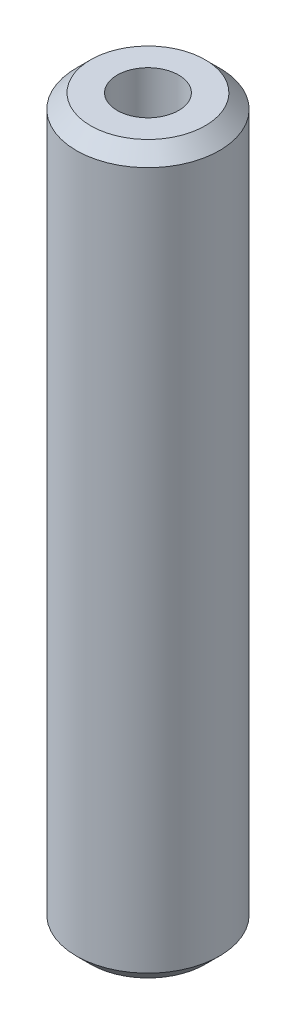
SolidWorks part; units mm, degrees
ref_plane "Front Plane" through (0, 0, 0) normal (0, 0, 1) x (1, 0, 0)
ref_plane "Top Plane" through (0, 0, 0) normal (0, 1, 0) x (1, 0, 0)
ref_plane "Right Plane" through (0, 0, 0) normal (1, 0, 0) x (0, 0, -1)
sketch "Sketch1" plane through (0, 0, 0) normal (0, 1, 0) x (1, 0, 0)
  circle A0 centre (0, 0) radius 25
  dimension "SHAFT_OD" = 50
extrude "Boss-Extrude1" add sketch "Sketch1" along normal blind 253.6707
sketch "Sketch2" plane through (0, 0, 0) normal (0, 1, 0) x (1, 0, 0)
  circle A0 centre (0, 0) radius 10.7359
  dimension "BORE_D" = 21.4719
extrude "Cut-Extrude1" cut sketch "Sketch2" along normal through all
chamfer "Chamfer1" distance 4.9976 angle 45 2 edges at (0, 253.6707, 25) (0, 0, 25)
